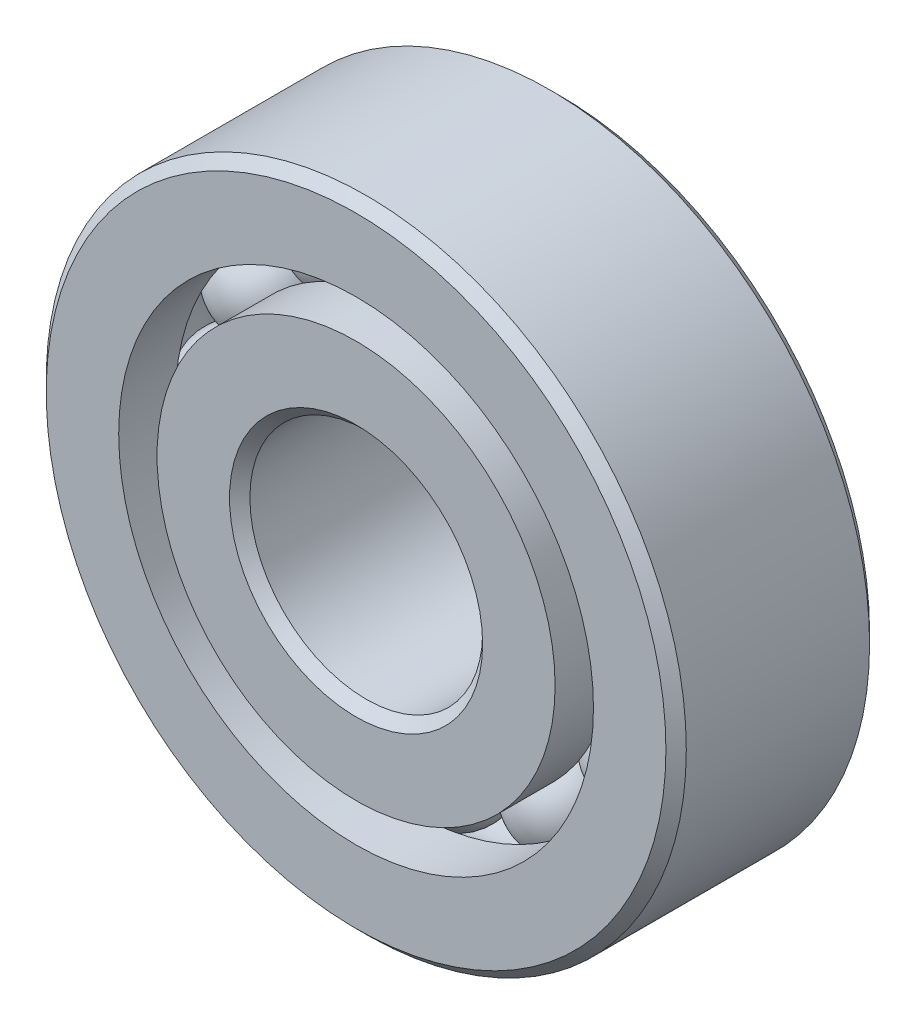
SolidWorks part; units mm, degrees
ref_plane "Front Plane" through (0, 0, 0) normal (0, 0, 1) x (1, 0, 0)
ref_plane "Top Plane" through (0, 0, 0) normal (0, 1, 0) x (1, 0, 0)
ref_plane "Right Plane" through (0, 0, 0) normal (1, 0, 0) x (0, 0, -1)
sketch "Sketch1" plane through (0, 0, 0) normal (1, 0, 0) x (0, 0, -1)
  line L0 (-3.5, 0) -> (3.5, 0) construction
  line L1 (0, 11) -> (0, -11) construction
  line L2 (3.15, 11) -> (-3.15, 11)
  line L3 (-3.15, 11) -> (-3.5, 10.65)
  line L4 (-3.5, 10.65) -> (-3.5, 8.1593)
  line L5 (-3.5, 8.1593) -> (-1.5556, 8.1593)
  line L6 (3.5, 8.1593) -> (1.5556, 8.1593)
  line L7 (3.5, 10.65) -> (3.5, 8.1593)
  line L8 (3.15, 11) -> (3.5, 10.65)
  line L9 (0, 11) -> (0, 7.5) construction
  line L10 (0, 7.5) -> (0, 4) construction
  arc A0 (-1.5556, 8.1593) -> (1.5556, 8.1593) centre (0, 7.5) cw
  point P14 (0, 4)
  dimension "D3" = 3.1111
  dimension "D1" = 45
  dimension "Width" = 7
  dimension "OD" = 22
  dimension "D2" = 0.35
  dimension "Shaft Dia" = 8
  dimension "D4" = 0.6593
revolve "Revolve1" add sketch "Sketch1" angle 360 about L0
sketch "Sketch3" plane through (0, 0, 0) normal (1, 0, 0) x (0, 0, -1)
  line L0 (-3.5, 6.8407) -> (-1.5556, 6.8407)
  line L1 (0, 11) -> (0, -11) construction
  line L2 (-3.5, 10.65) -> (-3.5, 8.1593) construction
  line L3 (-3.5, 6.8407) -> (-3.5, 4.35)
  line L4 (-3.15, 11) -> (-3.5, 10.65) construction
  line L5 (-3.5, 4.35) -> (-3.15, 4)
  line L6 (-3.15, 4) -> (3.15, 4)
  line L7 (3.15, 11) -> (3.15, -11) construction
  line L8 (3.15, 4) -> (3.5, 4.35)
  line L9 (3.5, -10.65) -> (3.5, 10.65) construction
  line L10 (3.5, 4.35) -> (3.5, 6.8407)
  line L11 (3.5, 6.8407) -> (1.5556, 6.8407)
  line L13 (3.15, 11) -> (3.5, 10.65) construction
  arc A0 (1.5556, 8.1593) -> (-1.5556, 8.1593) centre (0, 7.5) ccw construction
  arc A1 (1.5556, 6.8407) -> (-1.5556, 6.8407) centre (0, 7.5) cw
revolve "Revolve3" add sketch "Sketch3" angle 360 about L0
sketch "Sketch4" plane through (0, 0, 0) normal (1, 0, 0) x (0, 0, -1)
  line L0 (-1.6895, 7.5) -> (1.6895, 7.5)
  arc A2 (-1.6895, 7.5) -> (1.6895, 7.5) centre (0, 7.5) cw
  arc A3 (1.5556, 8.1593) -> (-1.5556, 8.1593) centre (0, 7.5) ccw construction
revolve "Revolve4" add sketch "Sketch4" angle 360 about L0
ref_axis "Axis1" through (0, 0, -3.5) along (0, 0, 1)
pattern_circular "CirPattern1" count 12 every 30 about axis through (0, 0, -3.5) along (0, 0, 1) of bodies 104
sketch "Sketch5" plane through (0, 0, 0) normal (1, 0, 0) x (0, 0, -1)
  line L0 (-3.5, 8.1593) -> (-1.5556, 8.1593) construction
  line L1 (-3.325, 8.1593) -> (-1.6895, 8.1593)
  line L2 (-3.325, 8.1593) -> (-3.325, 6.8407)
  line L3 (-3.325, 6.8407) -> (-1.6895, 6.8407)
  line L4 (-1.6895, 8.1593) -> (-1.6895, 6.8407)
  line L5 (-3.5, 6.8407) -> (-1.5556, 6.8407) construction
  line L6 (3.5, 8.1593) -> (1.5556, 8.1593) construction
  line L7 (3.325, 8.1593) -> (1.6895, 8.1593)
  line L8 (3.325, 8.1593) -> (3.325, 6.8407)
  line L9 (3.325, 6.8407) -> (1.6895, 6.8407)
  line L10 (1.6895, 8.1593) -> (1.6895, 6.8407)
  line L11 (3.5, 6.8407) -> (1.5556, 6.8407) construction
  line L12 (-3.15, 11) -> (-3.5, 10.65) construction
  point P18 (-3.325, 10.825)
equation "\"D2@Sketch1\" = \"Width@Sketch1\"*.05"
equation "\"D3@Sketch1\" = \"Width@Sketch1\"/2.25"
equation "\"D4@Sketch1\" = (((\"OD@Sketch1\"-\"Width@Sketch1\")/2)/3.25)/3.5"
equation "\"D2@CirPattern1\" = 360/\"Balls@CirPattern1\""
